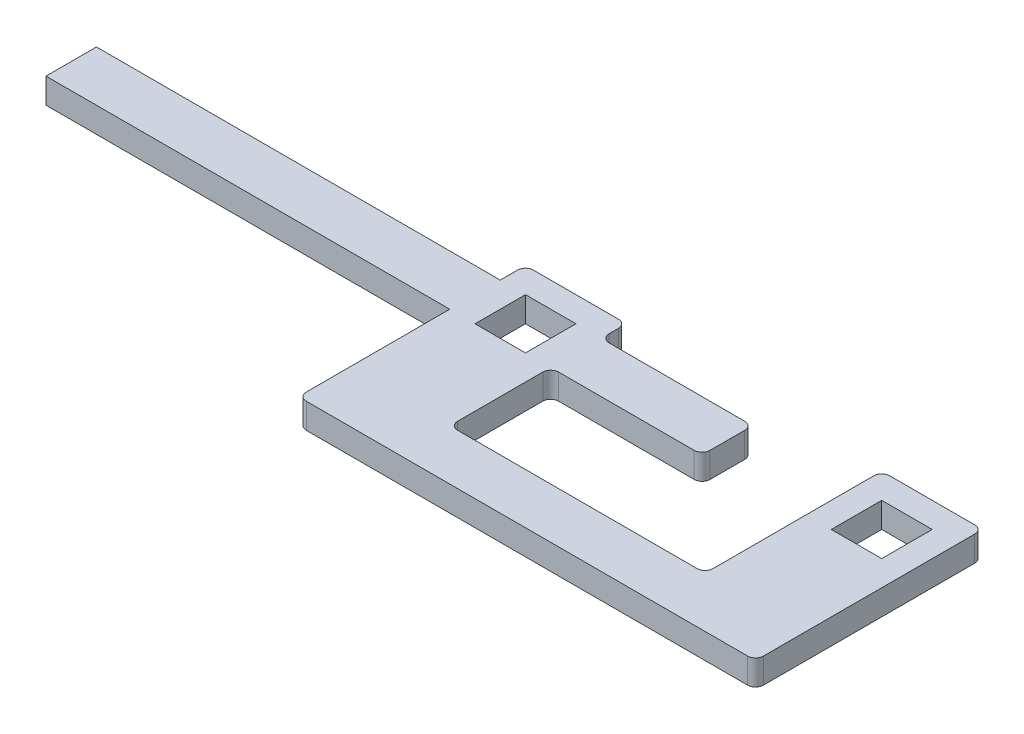
SolidWorks part; units mm, degrees
material "Beech"
ref_plane "Front Plane" through (0, 0, 0) normal (0, 0, 1) x (1, 0, 0)
ref_plane "Top Plane" through (0, 0, 0) normal (0, 1, 0) x (1, 0, 0)
ref_plane "Right Plane" through (0, 0, 0) normal (1, 0, 0) x (0, 0, -1)
sketch "Sketch1" plane through (0, 0, 0) normal (0, 1, 0) x (1, 0, 0)
  line L0 (0, 0) -> (0, 19.05)
  line L1 (0, 0) -> (19.05, 0)
  line L2 (0, 28.575) -> (12.7, 28.575)
  line L3 (12.7, 6.35) -> (12.7, 19.05)
  line L4 (44.825, 28.575) -> (44.825, 6.35)
  line L5 (44.825, 28.575) -> (57.525, 28.575)
  line L6 (42.65, 0) -> (57.525, 0)
  line L7 (57.525, 28.575) -> (57.525, 0)
  line L8 (12.7, 6.35) -> (44.825, 6.35)
  line L10 (12.7, 19.05) -> (31.75, 19.05)
  line L11 (19.05, 0) -> (42.65, 0)
  line L12 (3.175, 25.4) -> (3.175, 19.05)
  line L13 (3.175, 25.4) -> (9.525, 25.4)
  line L14 (3.175, 19.05) -> (9.525, 19.05)
  line L15 (9.525, 25.4) -> (9.525, 19.05)
  line L16 (48, 25.4) -> (48, 19.05)
  line L17 (48, 25.4) -> (54.35, 25.4)
  line L18 (48, 19.05) -> (54.35, 19.05)
  line L19 (54.35, 25.4) -> (54.35, 19.05)
  line L20 (0, 25.4) -> (-50.8, 25.4)
  line L21 (12.7, 25.4) -> (31.75, 25.4)
  line L22 (-50.8, 25.4) -> (-50.8, 19.05)
  line L23 (0, 19.05) -> (-50.8, 19.05)
  line L24 (0, 25.4) -> (0, 28.575)
  line L25 (31.75, 19.05) -> (31.75, 25.4)
  line L26 (12.7, 25.4) -> (12.7, 28.575)
  dimension "D1" = 6.35
  dimension "D2" = 6.35
  dimension "D3" = 6.35
  dimension "D4" = 6.35
  dimension "D5" = 44.825
  dimension "D6" = 3.175
  dimension "D7" = 19.05
  dimension "D8" = 3.175
  dimension "D9" = 3.175
  dimension "D10" = 3.175
  dimension "D11" = 3.175
  dimension "D12" = 3.175
  dimension "D13" = 19.05
  dimension "D14" = 50.8
  dimension "D15" = 6.35
  dimension "D16" = 6.35
  dimension "D17" = 19.05
extrude "Elastic_Extrude" add sketch "Sketch1" along normal blind 3.175
fillet "Elastic_CornerFillet" radius 1 12 edges at (12.7, 1.5875, -6.35) (44.825, 1.5875, -6.35) (44.825, 1.5875, -28.575) (57.525, 1.5875, -28.575) (57.525, 1.5875, 0) (0, 1.5875, 0) (0, 1.5875, -28.575) (12.7, 1.5875, -19.05) (31.75, 1.5875, -19.05) (31.75, 1.5875, -25.4) (12.7, 1.5875, -25.4) (12.7, 1.5875, -28.575)
equation "\"CageLeftBottomEdge\"=22.11mm"
equation "\"CageLeftTopEdge\"=22.11mm"
equation "\"CageRightBottomEdge\"=21.63mm"
equation "\"CageRightTopEdge\"=21.63mm"
equation "\"CageHeight\"=86.04mm"
equation "\"CageLength\"=73.76mm"
equation "\"CageTopScrewClearance\"=10mm"
equation "\"CageBottomScrewClearance\"=25mm"
equation "\"CageLeftTopDepth\"= 11.65mm"
equation "\"CageLeftBottomDepth\"=11.11mm"
equation "\"CageLeftTopHeight\"=8.56175mm"
equation "\"CageLeftBottomHeight\"=16mm"
equation "\"CageRightTopDepth\"= 11.05mm"
equation "\"CageRightBottomDepth\"=10.58mm"
equation "\"CageRightTopHeight\"=9.6mm"
equation "\"CageRightBottomHeight\"=15.49mm"
equation "\"CageLeftTopChannelDepth\"=2.41908mm"
equation "\"CageLeftBottomChannelDepth\"=2.588mm"
equation "\"CageLeftChannelHeight\"=11.7mm"
equation "\"CageRightTopChannelDepth\"=2.32mm"
equation "\"CageRightBottomChannelDepth\"=2.318mm"
equation "\"CageRightChannelHeight\"=10mm"
equation "\"CageChanRelHeight\"=23.99mm"
equation "\"CageChanRelDepth\"=5.492mm"
equation "\"CageChamberRadius\"=16.261mm"
equation "\"CageScrewDiameter\"=4.8mm"
equation "\"CageSetScrewDiameter\"=3.5mm"
equation "\"CageAxleRadius\"=6.639mm"
equation "\"CageAxleKeyHeight\"=1.619mm"
equation "\"CageAxleKeyWidth\"=2.662mm"
equation "\"CageHoseWindowWidth\"=16.29mm"
equation "\"CageHoseWindowHeight\"=26.5mm"
equation "\"CageHoseWindow-Edge\"=8.89mm"
equation "\"CageScrew-VerticalEdge\"=5.0mm"
equation "\"CageScrew-HorizontalEdge\"=7.5mm"
equation "\"CageScrew-HoseCornerScrewEdge\"=4.45mm"
equation "\"CageAxle-BottomEdge\"=56.05mm"
equation "\"CageAxle-FrontEdge\"=46.03mm"
equation "\"CageBackSetScrew-Axle\"=40mm"
equation "\"CageFrontSetScrew-Axle\"=22mm"
equation "\"CageVelocityWindow-BackEdge\"=34.8mm"
equation "\"CageVelocityWindow-BottomEdge\"=27.55mm"
equation "\"CageVelocityWindowHeight\"=22.29mm"
equation "\"CageVelocityWindowWidth\"=12.61mm"
equation "\"TriggerSlot-BottomEdge\"=6.35mm"
equation "\"TriggerSlot-FrontEdge\"=15mm"
equation "\"TriggerSlotSize\"=6.7mm"
equation "\"TriggerRackOffset\"=.236224in"
equation "\"TriggerSlotSizeInt\"=.25in"
equation "\"MotorMountLegLength\"=.25in"
equation "\"GearOffset\"=.264907in"
equation "\"TriggerSlotSpacing\"=.25in"
equation "\"TriggerMiniSlotWidth\"=3.5mm"
equation "\"TriggerRackWidth\"=6.5mm"
equation "\"TGMGearFaceDiameter\"=24.40mm"
equation "\"TGMCylinderLength\"=15.00mm"
equation "\"TGMScrewHole-Center\"=8.70mm"
equation "\"TGMScrewHoleDiameter\"=5.04mm"
equation "\"TGMCenterHoleDiameter\"=9.50mm"
equation "\"TGMShaftCollarSideLength\"=19.00mm"
equation "\"TGMShaftCollarDockingDepth\"=7.00mm"
equation "\"whitemotordepth\"=11.27mm"
equation "\"whitemotorbackdepth\"=3.845mm"
equation "\"whitemotoraxledepth\" = 3.5mm"
equation "\"whitemotoraxleoffset\"=11.4mm"
equation "\"whitemotorwidth\"=12.07mm"
equation "\"whitemotorheight\"=16.68mm"
equation "\"whitemotorcylinderlength\" =13.04mm"
equation "\"whitemotorcylinderradius\"=3.845mm"
equation "\"whitemotorcylinderoffset\"=2.35mm"
equation "\"whitemotorcutoutlength\"=1.88mm"
equation "\"whitemotorouterrad\"=5mm"
equation "\"D4@Sketch1\"=\"elasticrackpegsize\""
equation "\"elasticrackpegspacing\"=1.76476378in"
equation "\"D5@Sketch1\"=\"elasticrackpegspacing\""
equation "\"D6@Sketch1\"=\"elasticrackpegbuffer\""
equation "\"elasticrackpegsize\"=.25in"
equation "\"D1@Sketch1\"=\"elasticrackpegsize\""
equation "\"D2@Sketch1\"=\"elasticrackpegsize\""
equation "\"D3@Sketch1\"=\"elasticrackpegsize\""
equation "\"elasticracklength\"=2in"
equation "\"D14@Sketch1\"=\"elasticracklength\""
equation "\"elasticrackpegbuffer\"=.125in"
equation "\"D11@Sketch1\"=\"elasticrackpegbuffer\""
equation "\"D12@Sketch1\"=\"elasticrackpegbuffer\""
equation "\"D10@Sketch1\"=\"elasticrackpegbuffer\""
equation "\"D9@Sketch1\"=\"elasticrackpegbuffer\""
equation "\"D8@Sketch1\"=\"elasticrackpegbuffer\""
equation "\"elasticbaybuffer\"=.25in"
equation "\"D15@Sketch1\"=\"elasticbaybuffer\""
equation "\"D16@Sketch1\"=\"elasticbaybuffer\""
equation "\"whitemotorinnerrad\"=2.95mm"
equation "\"elasticbaydepth\"=.75in"
equation "\"D7@Sketch1\"=\"elasticbaydepth\""
equation "\"D13@Sketch1\"=\"elasticbaydepth\""
equation "\"D17@Sketch1\"=\"elasticbaydepth\""
equation "\"elasticdepth\"=.125in"
equation "\"D1@Elastic_Extrude\"=\"elasticdepth\""
equation "\"motormountwidth\"=12mm"
equation "\"motormountcornerfillet\"=3mm"
equation "\"pandiscradius\"=14in"
equation "\"towermaterialwidth\"=.25in"
equation "\"towerslotlength\"=.5in"
equation "\"towermarkerspace\"=5in"
equation "\"towerslothorizoffset\"=1in"
equation "\"towerslothorizspacing\"=2in"
equation "\"towerslotvertoffset\"=3in"
equation "\"towerslotvertspacing\"=2in"
equation "\"towerheight\"=12in"
equation "\"towerupslot\"=1in"
equation "\"toweraxle\"=.5in"
equation "\"towerplatslotoffset\"=1.5in"
equation "\"towermotorpanelheight\"=10in"
equation "\"towerplatdepth\"=2in"
equation "\"stepperouterrad\"=10mm"
equation "\"stepperscrewsize\"=3.45mm"
equation "\"stepperscrewc2c\"=49.5mm"
equation "\"stepperdepthoffset\"=24mm"
equation "\"stepperhorizoffset\"=22.91mm"
equation "\"shaftslotOD\"=18.8mm"
equation "\"shaftslotID\"=13.28mm"
equation "\"shaftkeywidth\"=2.67mm"
equation "\"shaftkeydepth\"=1.8mm"
equation "\"shaftcollartotaldepth\"=12.5mm"
equation "\"shaftsquaredepth\"=6mm"
equation "\"shaftsetscrewsize\"=3.5mm"
equation "\"shaftkeytightdepth\"=1.85mm"
equation "\"shaftslottightID\"=12.78mm"
equation "\"shaftsetscrewoffset\"=9mm"
equation "\"cagecollartotaldepth\"=10mm"
equation "\"cagecollartotalwidth\"=35mm"
equation "\"cagecollarbasedepth\"=4mm"
